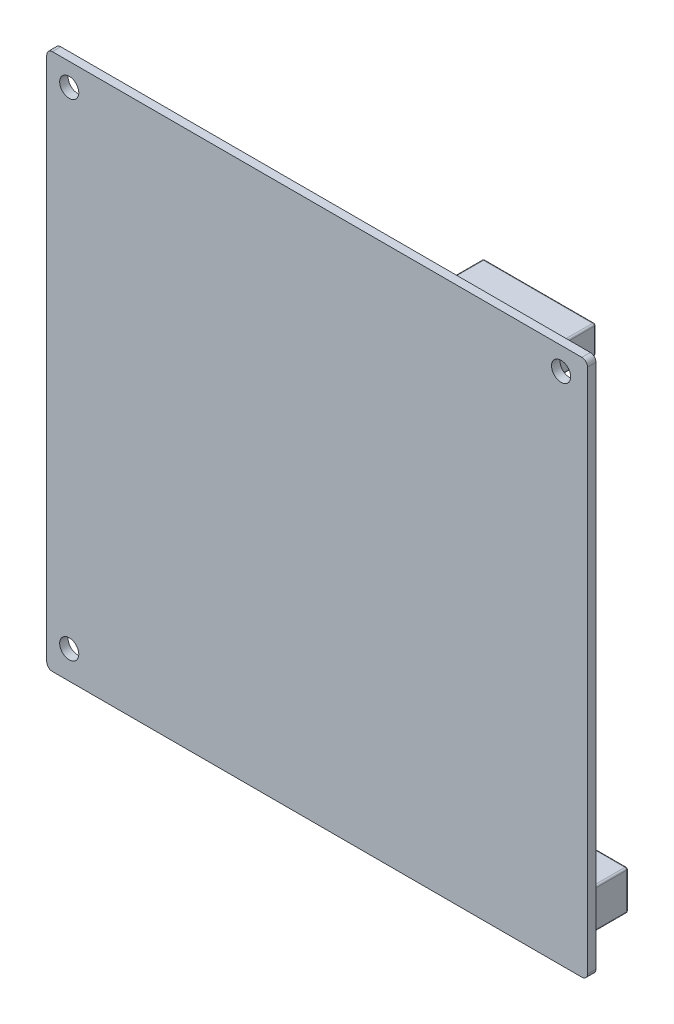
SolidWorks part; units mm, degrees
ref_plane "Front Plane" through (0, 0, 0) normal (0, 0, 1) x (1, 0, 0)
ref_plane "Top Plane" through (0, 0, 0) normal (0, 1, 0) x (1, 0, 0)
ref_plane "Right Plane" through (0, 0, 0) normal (1, 0, 0) x (0, 0, -1)
sketch "Sketch1" plane through (0, 0, 0) normal (0, 0, 1) x (1, 0, 0)
  line L1 (-47.1, 47.75) -> (47.1, 47.75)
  line L2 (-48.1, 46.75) -> (-48.1, -46.75)
  line L3 (-47.1, -47.75) -> (47.1, -47.75)
  line L4 (48.1, 46.75) -> (48.1, -46.75)
  line L5 (-48.1, 47.75) -> (48.1, -47.75) construction
  line L6 (-48.1, -47.75) -> (48.1, 47.75) construction
  arc A0 (-48.1, -46.75) -> (-47.1, -47.75) centre (-47.1, -46.75) ccw
  arc A1 (47.1, -47.75) -> (48.1, -46.75) centre (47.1, -46.75) ccw
  arc A2 (47.1, 47.75) -> (48.1, 46.75) centre (47.1, 46.75) cw
  arc A3 (-47.1, 47.75) -> (-48.1, 46.75) centre (-47.1, 46.75) ccw
  circle A4 centre (-44.1, 43.75) radius 1.7
  circle A5 centre (-44.1, -42.75) radius 1.7
  circle A6 centre (43.4, 43.75) radius 1.7
  point P0 (0, 0)
  point P22 (43.3949, 44.6953)
  point P23 (0, 0)
  dimension "D3" = 1
  dimension "D4" = 3.4
  dimension "D5" = 3.4
  dimension "D6" = 86.5
  dimension "D7" = 3.4
  dimension "D9" = 4
  dimension "D10" = 4
  dimension "D1" = 95.5
  dimension "D2" = 96.2
  dimension "D8" = 87.5
extrude "Boss-Extrude1" add sketch "Sketch1" along normal blind 1.5
sketch "Sketch2" plane through (0, 0, 0) normal (0, 0, -1) x (-1, 0, 0)
  line L1 (-43.8464, -38.1931) -> (-33.8464, -38.1931)
  line L2 (-43.8464, -38.1931) -> (-43.8464, -45.1931)
  line L3 (-43.8464, -45.1931) -> (-33.8464, -45.1931)
  line L4 (-33.8464, -38.1931) -> (-33.8464, -45.1931)
  dimension "D1" = 10
  dimension "D2" = 7
extrude "Boss-Extrude2" add sketch "Sketch2" along normal blind 10
fillet "Fillet1" radius 0.3 12 edges at (43.8464, -41.6931, 0) (43.8464, -38.1931, -5) (38.8464, -38.1931, 0) (33.8464, -38.1931, -5) (33.8464, -41.6931, 0) (43.8464, -45.1931, -5) (33.8464, -45.1931, -5) (38.8464, -45.1931, 0) (38.8464, -38.1931, -10) (33.8464, -41.6931, -10) (38.8464, -45.1931, -10) (43.8464, -41.6931, -10)
sketch "Sketch3" plane through (0, 0, 0) normal (0, 0, -1) x (-1, 0, 0)
  line L0 (-47.1, 47.75) -> (47.1, 47.75) construction
  line L1 (39.1, 27.75) -> (44.1, 27.75)
  line L2 (39.1, 27.75) -> (39.1, -32.25)
  line L3 (39.1, -32.25) -> (44.1, -32.25)
  line L4 (44.1, 27.75) -> (44.1, -32.25)
  line L5 (48.1, 46.75) -> (48.1, -46.75) construction
  line L6 (-48.1, -46.75) -> (-48.1, 46.75) construction
  line L7 (-38.1, 42.75) -> (-18.1, 42.75)
  line L8 (-38.1, 42.75) -> (-38.1, 37.75)
  line L9 (-38.1, 37.75) -> (-18.1, 37.75)
  line L10 (-18.1, 42.75) -> (-18.1, 37.75)
  line L12 (-8.9743, -38.9109) -> (-3.9743, -38.9109)
  line L13 (-8.9743, -38.9109) -> (-8.9743, -43.9109)
  line L14 (-8.9743, -43.9109) -> (-3.9743, -43.9109)
  line L15 (-3.9743, -38.9109) -> (-3.9743, -43.9109)
  circle A0 centre (-24.6458, -38.9109) radius 3.5
  circle A1 centre (-18.1, -38.9109) radius 2.5
  dimension "D9" = 7
  dimension "D10" = 5
  dimension "D1" = 5
  dimension "D2" = 60
  dimension "D3" = 20
  dimension "D4" = 4
  dimension "D5" = 20
  dimension "D6" = 5
  dimension "D7" = 5
  dimension "D8" = 10
  dimension "D11" = 5
  dimension "D12" = 5
extrude "Boss-Extrude3" add sketch "Sketch3" along normal blind 10
fillet "Fillet2" radius 0.3 40 edges at (-39.1, -2.25, 0) (-39.1, -32.25, -5) (-41.6, -32.25, 0) (-44.1, -32.25, -5) (-44.1, -2.25, 0) (-44.1, 27.75, -5) (-39.1, 27.75, -5) (-41.6, 27.75, 0) (-41.6, 27.75, -10) (-44.1, -2.25, -10) (-41.6, -32.25, -10) (-39.1, -2.25, -10) (38.1, 40.25, 0) (38.1, 37.75, -5) (28.1, 37.75, 0) (18.1, 37.75, -5) (18.1, 40.25, 0) (18.1, 42.75, -5) (38.1, 42.75, -5) (28.1, 42.75, 0) (28.1, 42.75, -10) (18.1, 40.25, -10) (28.1, 37.75, -10) (38.1, 40.25, -10) (28.1458, -38.9109, 0) (21.1458, -38.9109, -10) (20.6, -38.9109, 0) (15.6, -38.9109, -10) (8.9743, -41.4109, 0) (8.9743, -43.9109, -5) (6.4743, -43.9109, 0) (3.9743, -43.9109, -5) (3.9743, -41.4109, 0) (3.9743, -38.9109, -5) (8.9743, -38.9109, -5) (6.4743, -38.9109, 0) (6.4743, -38.9109, -10) (3.9743, -41.4109, -10) (6.4743, -43.9109, -10) (8.9743, -41.4109, -10)
